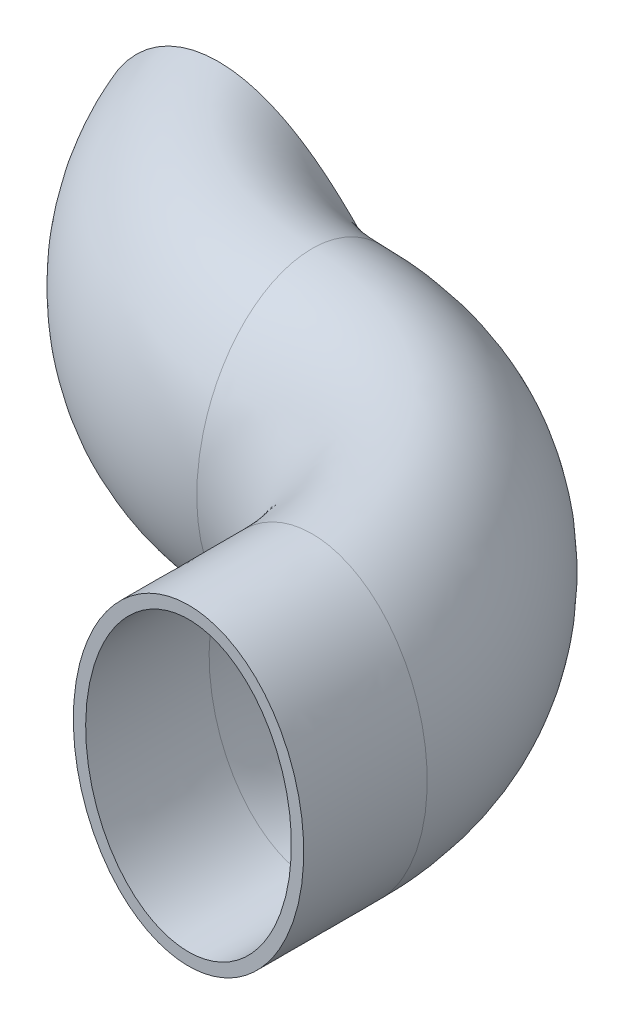
SolidWorks part; units mm, degrees
ref_plane "Alzado" through (0, 0, 0) normal (0, 0, 1) x (1, 0, 0)
ref_plane "Planta" through (0, 0, 0) normal (0, 1, 0) x (1, 0, 0)
ref_plane "Vista lateral" through (0, 0, 0) normal (1, 0, 0) x (0, 0, -1)
sketch "Croquis2" plane through (0, 0, 0) normal (0, 0, 1) x (1, 0, 0)
  ellipse E0 centre (0, 0) end of major axis (0, -35) minor radius 25
  ellipse E1 centre (0, 0) end of major axis (0, 38) minor radius 28
  point P1 (0, 0)
  dimension "D1" = 35
  dimension "D2" = 25
  dimension "D3" = 3
  dimension "D4" = 3
sketch "Croquis3" plane through (0, 0, 0) normal (0, 1, 0) x (1, 0, 0)
  line L0 (0, 0) -> (0, 30)
  arc A0 (0, 30) -> (-60, 90) centre (-60, 30) ccw
  arc A1 (-60, 90) -> (-120, 150) centre (-60, 150) cw
  point P7 (-80, 93.4315)
  point P8 (-117.8934, 134.2408)
  point P9 (-76.3712, 89.9241)
  point P10 (-60.0674, 68.0774)
  point P11 (-71.9376, 79.4612)
  point P12 (-70, 79.033)
  point P13 (-82.8427, 102.2918)
  point P14 (-83.3333, 97.8892)
  point P15 (-49.2286, 89.0252)
  point P16 (-54.7082, 89.7662)
  point P17 (0, 0)
  point P18 (0, 0)
  dimension "D2" = 60
  dimension "D4" = 60
  dimension "D3" = 30
sweep "Barrer6" add profiles "Croquis2" path "Croquis3"
sketch "Croquis21" plane through (0, 0, 0) normal (0, 1, 0) x (1, 0, 0)
  line L1 (-60, 118) -> (-174.7395, 118)
  line L2 (-60, 118) -> (-60, 154.181)
  line L3 (-60, 154.181) -> (-174.7395, 154.181)
  line L4 (-174.7395, 118) -> (-174.7395, 154.181)
  arc A0 (28, 30) -> (-60, 118) centre (-60, 30) ccw construction
  arc A1 (-92, 150) -> (-60, 118) centre (-60, 150) ccw construction
  dimension "D1" = 36.181
  dimension "D2" = 114.7395
extrude "Cortar-Extruir1" cut sketch "Croquis21" against normal blind 50 and the other way blind 50
